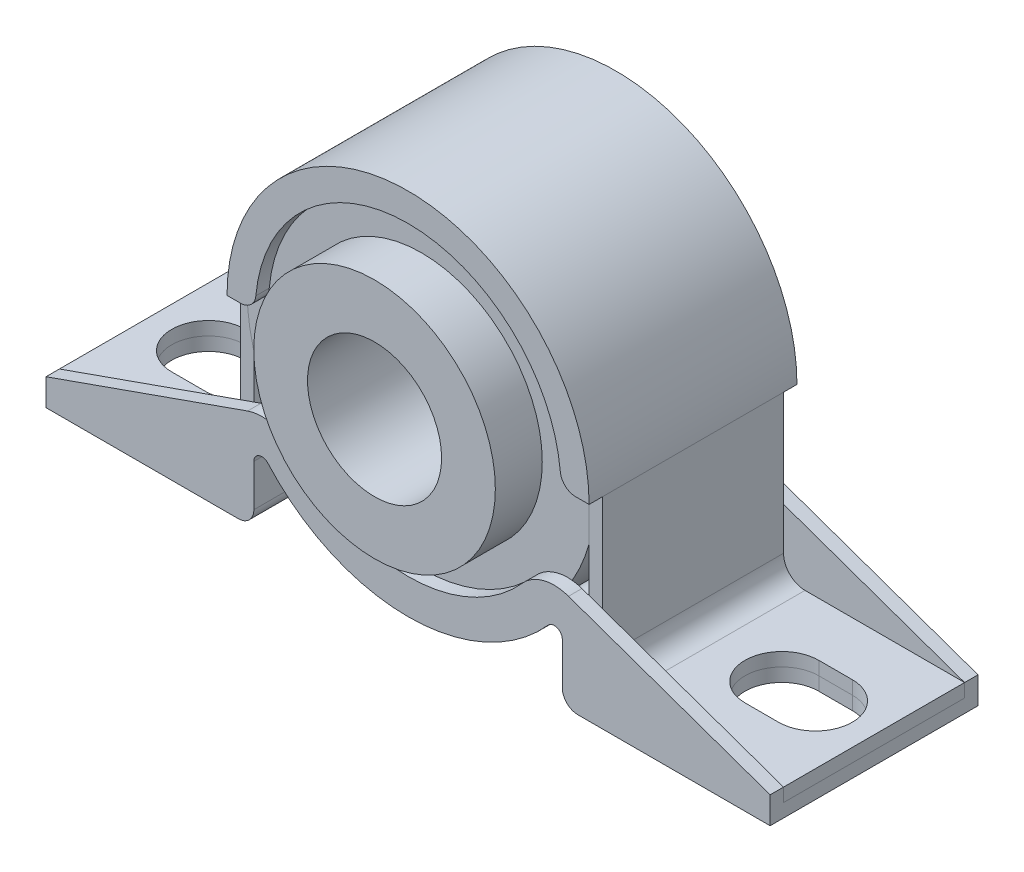
SolidWorks part; units mm, degrees
ref_plane "Front" through (0, 0, 0) normal (0, 0, 1) x (1, 0, 0)
ref_plane "Top" through (0, 0, 0) normal (0, 1, 0) x (1, 0, 0)
ref_plane "Right" through (0, 0, 0) normal (1, 0, 0) x (0, 0, -1)
sketch "Sketch1" plane through (0, 0, 0) normal (0, 0, 1) x (1, 0, 0)
  line L1 (-23.9712, -19.05) -> (-42.8625, -19.05) construction
  line L2 (-42.8625, -19.05) -> (-42.8625, -22.225) construction
  line L3 (-42.8625, -22.225) -> (42.8625, -22.225) construction
  line L6 (0, 0) -> (0, -22.225) construction
  line L9 (42.8625, -22.225) -> (42.8625, -19.05) construction
  line L10 (42.8625, -19.05) -> (23.9713, -19.05) construction
  line L12 (-21.4313, 0) -> (-21.4312, -16.51) construction
  line L13 (-42.8625, -20.6375) -> (-19.8438, -20.6375)
  line L14 (21.4313, 0) -> (21.4313, -16.51) construction
  line L15 (-19.8438, -20.6375) -> (-19.8438, -15.42)
  line L16 (19.8438, -15.42) -> (19.8438, -20.6375)
  line L17 (19.8438, -20.6375) -> (42.8625, -20.6375)
  circle A0 centre (0, 0) radius 7.9375 construction
  circle A1 centre (0, 0) radius 14.3002 construction
  arc A2 (21.4313, 0) -> (-21.4313, 0) centre (0, 0) ccw construction
  arc A5 (-21.4312, -16.51) -> (-23.9712, -19.05) centre (-23.9712, -16.51) cw construction
  arc A6 (21.4313, -16.51) -> (23.9713, -19.05) centre (23.9713, -16.51) ccw construction
  arc A7 (-19.8438, -15.42) -> (-15.4074, -13.7301) centre (-17.3038, -15.42) cw
  arc A8 (-15.4074, -13.7301) -> (15.4074, -13.7301) centre (0, 0) ccw
  arc A9 (15.4074, -13.7301) -> (19.8438, -15.42) centre (17.3038, -15.42) cw
  dimension "D1" = 2.54
  dimension "Shaft Dia" = 15.875
  dimension "D2" = 1.5875
  dimension "K" = 28.6004
  dimension "w" = 43.6562
  dimension "h" = 22.225
  dimension "g" = 3.175
  dimension "a" = 85.725
extrude "Extrude-Thin2" add sketch "Sketch1" along normal mid plane 24.6062 thin thin type one direction wall 1.5875
sketch "Sketch4" plane through (0, 0, 12.3031) normal (0, 0, 1) x (1, 0, 0)
  line L0 (-42.8625, -19.05) -> (-18.9938, -10.6294)
  line L1 (18.9938, -10.6294) -> (42.8625, -19.05)
  line L2 (-23.9712, -19.05) -> (-42.8625, -19.05) construction
  line L3 (42.8625, -19.05) -> (23.9713, -19.05) construction
  line L10 (20.0978, -22.225) -> (42.8625, -22.225)
  line L11 (42.8625, -22.225) -> (42.8625, -20.6375)
  line L12 (42.8625, -20.6375) -> (20.0978, -20.6375)
  line L13 (19.8438, -20.3835) -> (19.8438, -15.42)
  line L14 (-19.8438, -15.42) -> (-19.8438, -20.3835)
  line L15 (-20.0978, -20.6375) -> (-42.8625, -20.6375)
  line L16 (-42.8625, -20.6375) -> (-42.8625, -22.225)
  line L17 (-42.8625, -22.225) -> (-20.0978, -22.225)
  line L18 (-18.2563, -20.3835) -> (-18.2563, -15.42)
  line L19 (18.2563, -15.42) -> (18.2563, -20.3835)
  line L20 (20.0978, -22.225) -> (42.8625, -22.225)
  line L21 (42.8625, -22.225) -> (42.8625, -19.05)
  line L26 (-42.8625, -19.05) -> (-42.8625, -22.225)
  line L27 (-42.8625, -22.225) -> (-20.0978, -22.225)
  line L28 (-18.2563, -20.3835) -> (-18.2563, -15.42)
  line L29 (18.2563, -15.42) -> (18.2563, -20.3835)
  arc A0 (-13.5111, -12.0403) -> (-18.9938, -10.6294) centre (-17.3038, -15.42) ccw
  arc A1 (18.9938, -10.6294) -> (13.5111, -12.0403) centre (17.3038, -15.42) ccw
  arc A2 (-13.5111, -12.0403) -> (13.5111, -12.0403) centre (0, 0) ccw
  arc A10 (19.8438, -20.3835) -> (20.0978, -20.6375) centre (20.0978, -20.3835) ccw
  arc A11 (19.8438, -15.42) -> (15.4074, -13.7301) centre (17.3038, -15.42) ccw
  arc A12 (-15.4074, -13.7301) -> (15.4074, -13.7301) centre (0, 0) ccw
  arc A13 (-15.4074, -13.7301) -> (-19.8438, -15.42) centre (-17.3038, -15.42) ccw
  arc A14 (-20.0978, -20.6375) -> (-19.8438, -20.3835) centre (-20.0978, -20.3835) ccw
  arc A15 (-20.0978, -22.225) -> (-18.2563, -20.3835) centre (-20.0978, -20.3835) ccw
  arc A17 (-16.5926, -14.7863) -> (16.5926, -14.7863) centre (0, 0) ccw
  arc A19 (18.2563, -20.3835) -> (20.0978, -22.225) centre (20.0978, -20.3835) ccw
  arc A21 (-16.5926, -14.7863) -> (-18.2563, -15.42) centre (-17.3038, -15.42) ccw
  arc A22 (-16.5926, -14.7863) -> (-18.2563, -15.42) centre (-17.3038, -15.42) ccw
  arc A23 (18.2563, -15.42) -> (16.5926, -14.7863) centre (17.3038, -15.42) ccw
  arc A24 (18.2563, -15.42) -> (16.5926, -14.7863) centre (17.3038, -15.42) ccw
  arc A25 (-20.0978, -22.225) -> (-18.2563, -20.3835) centre (-20.0978, -20.3835) ccw
  arc A27 (-16.5926, -14.7863) -> (16.5926, -14.7863) centre (0, 0) ccw
  arc A29 (18.2563, -20.3835) -> (20.0978, -22.225) centre (20.0978, -20.3835) ccw
  dimension "D2" = 5.08
  dimension "D1" = 0
extrude "Extrude1" add sketch "Sketch4" against normal blind 1.5875
mirror "Mirror1" about plane through (0, 0, 0) normal (0, 0, 1) of "Extrude1"
sketch "Sketch5" plane through (0, 0, 0) normal (0, 0, 1) x (1, 0, 0)
  line L0 (42.8625, -19.05) -> (23.9713, -19.05) construction
  line L1 (21.4313, 0) -> (21.4313, -16.51) construction
  line L2 (-21.4313, 0) -> (-21.4312, -16.51) construction
  line L3 (-23.9712, -19.05) -> (-42.8625, -19.05) construction
  line L4 (42.8625, -19.05) -> (23.9713, -19.05)
  line L5 (21.4313, 0) -> (21.4313, -16.51)
  line L6 (-21.4313, 0) -> (-21.4312, -16.51)
  line L7 (-23.9712, -19.05) -> (-42.8625, -19.05)
  arc A0 (21.4313, -16.51) -> (23.9713, -19.05) centre (23.9713, -16.51) ccw construction
  arc A1 (21.4313, 0) -> (-21.4313, 0) centre (0, 0) ccw construction
  arc A2 (-23.9712, -19.05) -> (-21.4312, -16.51) centre (-23.9712, -16.51) ccw construction
  arc A3 (21.4313, -16.51) -> (23.9713, -19.05) centre (23.9713, -16.51) ccw
  arc A4 (21.4313, 0) -> (-21.4313, 0) centre (0, 0) ccw
  arc A5 (-23.9712, -19.05) -> (-21.4312, -16.51) centre (-23.9712, -16.51) ccw
extrude "Extrude-Thin3" add sketch "Sketch5" along normal up to surface (10.7156 mm away) and the other way up to surface (10.7156 mm away) separate body thin up to face at (0, -17.0875, 10.7156) other way up to face at (0, -17.0875, -10.7156) thin type one direction reverse wall 1.5875
sketch "Sketch6" plane through (0, 0, -10.7156) normal (0, 0, -1) x (-1, 0, 0)
  line L0 (-21.4313, 0) -> (21.4313, 0) construction
  line L1 (-19.8438, 0) -> (-21.4313, 0)
  line L2 (21.4313, 0) -> (19.8438, 0)
  arc A0 (21.4313, 0) -> (-21.4313, 0) centre (0, 0) ccw construction
  arc A1 (21.4313, 0) -> (-21.4313, 0) centre (0, 0) ccw
  arc A2 (-13.5111, -12.0403) -> (13.5111, -12.0403) centre (0, 0) ccw construction
  arc A3 (-13.5111, -12.0403) -> (18.0975, 0) centre (0, 0) ccw construction
  arc A4 (18.021, 1.6624) -> (-18.021, 1.6624) centre (0, 0) ccw
  arc A5 (19.8438, 0) -> (-19.8438, 0) centre (0, 0) ccw construction
  arc A6 (19.8438, 0) -> (-19.8438, 0) centre (0, 0) ccw construction
  arc A7 (-19.8438, 0) -> (-18.021, 1.6624) centre (-19.8438, 1.8305) ccw
  arc A8 (19.8438, 0) -> (18.021, 1.6624) centre (19.8438, 1.8305) cw
extrude "Extrude2" add sketch "Sketch6" along normal blind 1.5875
mirror "Mirror2" about plane through (0, 0, 0) normal (0, 0, 1) of "Extrude2"
sketch "Sketch7" plane through (0, 0, 0) normal (0, 0, 1) x (1, 0, 0)
  circle A0 centre (0, 0) radius 20.6375
  circle A1 centre (0, 0) radius 14.3002
  circle A2 centre (0, 0) radius 14.3002 construction
  arc A3 (-15.4074, -13.7301) -> (15.4074, -13.7301) centre (0, 0) ccw construction
extrude "Extrude3" add sketch "Sketch7" along normal up to surface (10.7156 mm away) and the other way up to surface (10.7156 mm away) separate body up to face at (0, -17.0875, 10.7156) other way up to face at (0, -17.0875, -10.7156)
ref_plane "Plane1" through (0, 0, 16.2719) normal (0, 0, -1) x (-1, 0, 0)
sketch "Sketch8" plane through (0, 0, 16.2719) normal (0, 0, 1) x (1, 0, 0)
  circle A0 centre (0, 0) radius 14.3002 construction
  circle A1 centre (0, 0) radius 7.9375 construction
  circle A2 centre (0, 0) radius 14.3002
  circle A3 centre (0, 0) radius 7.9375
extrude "Extrude4" add sketch "Sketch8" against normal blind 21.9989 separate body
sketch "Sketch3" plane through (0, 0, 0) normal (0, 1, 0) x (1, 0, 0)
  line L2 (-35.9172, 0) -> (-31.9484, 0) construction
  line L3 (-31.9484, 0) -> (0, 0) construction
  line L4 (0, 0) -> (31.9484, 0) construction
  line L5 (31.9484, 0) -> (35.9172, 0) construction
  line L6 (-35.9172, 4.3656) -> (-31.9484, 4.3656)
  line L7 (-35.9172, -4.3656) -> (-31.9484, -4.3656)
  line L8 (31.9484, -4.3656) -> (35.9172, -4.3656)
  line L9 (35.9172, 4.3656) -> (31.9484, 4.3656)
  arc A0 (-35.9172, 4.3656) -> (-35.9172, -4.3656) centre (-35.9172, 0) ccw
  arc A1 (-31.9484, 4.3656) -> (-31.9484, -4.3656) centre (-31.9484, 0) cw
  arc A2 (31.9484, 4.3656) -> (31.9484, -4.3656) centre (31.9484, 0) ccw
  arc A3 (35.9172, 4.3656) -> (35.9172, -4.3656) centre (35.9172, 0) cw
  point P13 (33.9328, -4.3656)
  point P14 (-33.9328, -4.3656)
  dimension "D1" = 67.8656
  dimension "Slot Width" = 8.7312
  dimension "Slot Length" = 12.7
extrude "Cut-Extrude1" cut sketch "Sketch3" against normal through all
sketch "Sketch9" plane through (0, 0, 0) normal (1, 0, 0) x (0, 0, -1)
  line L0 (-16.2719, 0) -> (5.7271, 0) construction
  line L1 (-16.2719, 14.3002) -> (-16.2719, -14.3002) construction
  line L2 (5.7271, -7.9375) -> (5.7271, 7.9375) construction
equation "\"D2@Sketch1\"=\"g@Sketch1\"/2"
equation "\"D5@Extrude-Thin2\"=\"g@Sketch1\"/2"
equation "\"D1@Extrude1\"=\"g@Sketch1\"/2"
equation "\"D5@Extrude-Thin3\" = \"g@Sketch1\"/2"
equation "\"D1@Extrude2\"=\"g@Sketch1\"/2"
